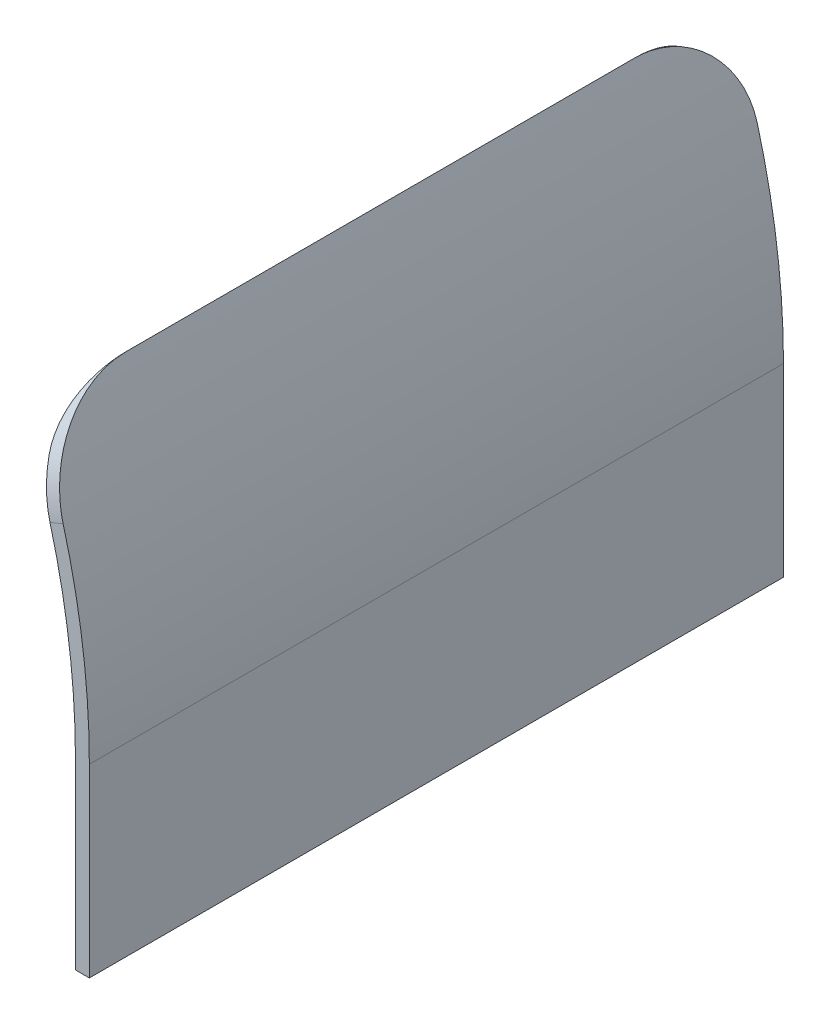
SolidWorks part; units mm, degrees
ref_plane "Front Plane" through (0, 0, 0) normal (0, 0, 1) x (1, 0, 0)
ref_plane "Top Plane" through (0, 0, 0) normal (0, 1, 0) x (1, 0, 0)
ref_plane "Right Plane" through (0, 0, 0) normal (1, 0, 0) x (0, 0, -1)
sketch "Sketch2" plane through (0, 0, 0) normal (0, 0, 1) x (1, 0, 0)
  line L0 (0, 0) -> (0, 197.0365)
  line L1 (0, 0) -> (15, 0)
  line L2 (15, 0) -> (15, 200)
  line L3 (-45.68, 505.624) -> (-59.5858, 500)
  arc A0 (0, 197.0365) -> (-59.5858, 500) centre (-800, 197.0365) ccw
  arc A1 (15, 200) -> (-45.68, 505.624) centre (-785, 200) ccw
  point P9 (-52.0778, 521.8566)
  point P10 (-50.8951, 517.9466)
  point P11 (-45.968, 506.3197)
  point P12 (-45.7103, 505.6972)
  dimension "D3" = 800
  dimension "D4" = 800
  dimension "D6" = 22.02
  dimension "D1" = 200
  dimension "D2" = 15
  dimension "D5" = 500
extrude "Boss-Extrude1" add sketch "Sketch2" along normal mid plane 750
fillet "Fillet1" radius 100 2 edges at (-52.6329, 502.812, -375) (-52.6329, 502.812, 375)
fillet "Fillet2" radius 100 1 edges at (-59.5858, 500, 0) tangent propagation no
